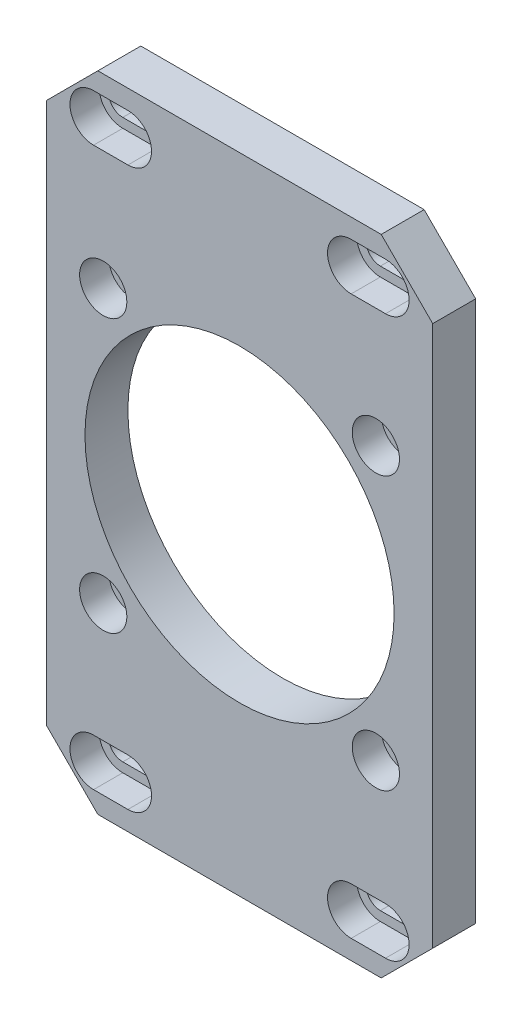
SolidWorks part; units mm, degrees
material "A3钢"
ref_plane "前视基准面" through (0, 0, 0) normal (0, 0, 1) x (1, 0, 0)
ref_plane "上视基准面" through (0, 0, 0) normal (0, 1, 0) x (1, 0, 0)
ref_plane "右视基准面" through (0, 0, 0) normal (1, 0, 0) x (0, 0, -1)
sketch "草图1" plane through (0, 0, 0) normal (0, 0, 1) x (1, 0, 0)
  line L1 (-45, -75) -> (45, -75)
  line L2 (-45, -75) -> (-45, 75)
  line L3 (-45, 75) -> (45, 75)
  line L4 (45, -75) -> (45, 75)
  line L5 (-45, -75) -> (45, 75) construction
  line L6 (-45, 75) -> (45, -75) construction
  point P0 (0, 0)
  dimension "D1" = 90
  dimension "D2" = 150
extrude "凸台-拉伸1" add sketch "草图1" along normal mid plane 10
sketch "草图2" plane through (0, 0, 5) normal (0, 0, 1) x (1, 0, 0)
  line L1 (-30, -65) -> (30, -65)
  line L2 (-30, -65) -> (-30, 65)
  line L3 (-30, 65) -> (30, 65)
  line L4 (30, -65) -> (30, 65)
  line L5 (-30, -65) -> (30, 65) construction
  line L6 (-30, 65) -> (30, -65) construction
  point P0 (0, 0)
  dimension "D1" = 60
  dimension "D2" = 130
sketch "草图4" plane through (0, 0, 5) normal (0, 0, 1) x (1, 0, 0)
  circle A0 centre (0, 0) radius 36
  dimension "D1" = 72
extrude "切除-拉伸1" cut sketch "草图4" against normal through all
sketch "草图7" plane through (0, 0, 5) normal (0, 0, 1) x (1, 0, 0)
  line L1 (-31.75, -31.75) -> (31.75, -31.75)
  line L2 (-31.75, -31.75) -> (-31.75, 31.75)
  line L3 (-31.75, 31.75) -> (31.75, 31.75)
  line L4 (31.75, -31.75) -> (31.75, 31.75)
  line L5 (-31.75, -31.75) -> (31.75, 31.75) construction
  line L6 (-31.75, 31.75) -> (31.75, -31.75) construction
  point P0 (0, 0)
  dimension "D1" = 63.5
  dimension "D2" = 63.5
hole_wizard "打孔尺寸(%根据)内六角圆柱头螺钉的类型3" positions "3D草图1" profile "草图8" counterbore size "M6" standard "GB" end condition through all
sketch3d "3D草图1"
  point P0 (-31.75, 31.75, 5)
  point P3 (31.75, 31.75, 5)
  point P6 (-31.75, -31.75, 5)
  point P9 (31.75, -31.75, 5)
sketch "草图8" plane through (-31.75, 31.75, 5) normal (1, 0, 0) x (0, -1, 0)
  line L0 (0, 0) -> (0, 10)
  line L1 (0, 10) -> (3.3, 10)
  line L3 (3.3, 10) -> (3.3, 6.8)
  line L4 (3.3, 6.8) -> (5.5, 6.8)
  line L5 (5.5, 6.8) -> (5.5, 0)
  line L7 (5.5, 0) -> (0, 0)
  line L11 (0, -6.35) -> (0, 107.95) construction
  dimension "通孔孔直径" = 6.6
  dimension "通孔孔深度" = 10
  dimension "柱形沉头孔直径" = 11
  dimension "柱形沉头孔深度" = 6.8
hole_wizard "打孔尺寸(%根据)内六角圆柱头螺钉的类型2" positions "草图9" profile "草图10" size "M6" standard "GB" slot yes end condition up to next
sketch "草图9" plane through (0, 0, 5) normal (0, 0, 1) x (1, 0, 0)
  line L0 (22.7, 65) -> (37.3, 65) construction
  point P0 (30, 65)
  point P5 (30, -65)
  point P8 (-30, -65)
  point P11 (-30, 65)
  dimension "D1" = 14.6
sketch "草图10" plane through (30, 65, 5) normal (1, 0, 0) x (0, -1, 0)
  line L0 (0, 0) -> (0, 10)
  line L1 (0, 10) -> (3.3, 10)
  line L3 (3.3, 10) -> (3.3, 6.8)
  line L4 (3.3, 6.8) -> (5.5, 6.8)
  line L5 (5.5, 6.8) -> (5.5, 0)
  line L7 (5.5, 0) -> (0, 0)
  line L11 (0, -6.35) -> (0, 107.95) construction
  dimension "通孔孔直径" = 6.6
  dimension "通孔孔深度" = 10
  dimension "柱形沉头孔直径" = 11
  dimension "柱形沉头孔深度" = 6.8
chamfer "倒角1" distance 12 angle 45 4 edges at (-45, 75, 0) (45, 75, 0) (-45, -75, 0) (45, -75, 0)
